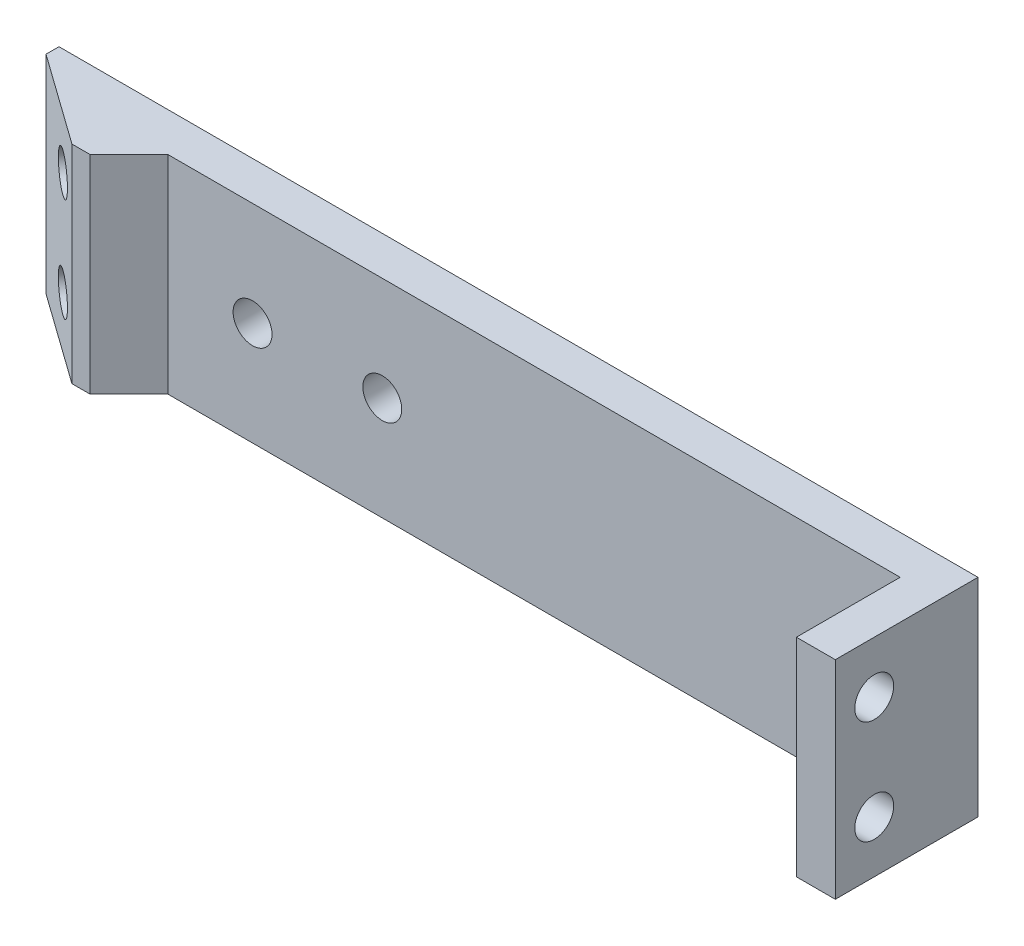
SolidWorks part; units mm, degrees
ref_plane "Front Plane" through (0, 0, 0) normal (0, 0, 1) x (1, 0, 0)
ref_plane "Top Plane" through (0, 0, 0) normal (0, 1, 0) x (1, 0, 0)
ref_plane "Right Plane" through (0, 0, 0) normal (1, 0, 0) x (0, 0, -1)
sketch "Sketch1" plane through (0, 0, 0) normal (0, 0, 1) x (1, 0, 0)
  line L1 (-35.425, -8) -> (35.425, -8)
  line L2 (-35.425, -8) -> (-35.425, 8)
  line L3 (-35.425, 8) -> (35.425, 8)
  line L4 (35.425, -8) -> (35.425, 8)
  line L5 (-35.425, -8) -> (35.425, 8) construction
  line L6 (-35.425, 8) -> (35.425, -8) construction
  point P0 (0, 0)
  dimension "D1" = 70.85
  dimension "D2" = 16
extrude "Boss-Extrude1" add sketch "Sketch1" along normal blind 3
sketch "Sketch2" plane through (0, 0, 3) normal (0, 0, 1) x (1, 0, 0)
  line L0 (-35.425, -8) -> (35.425, -8) construction
  line L1 (-35.425, 8) -> (-27.025, 8)
  line L2 (-35.425, 8) -> (-35.425, -8)
  line L3 (-35.425, -8) -> (-27.025, -8)
  line L4 (-27.025, 8) -> (-27.025, -8)
  dimension "D1" = 8.4
extrude "Boss-Extrude2" add sketch "Sketch2" along normal blind 3
chamfer "Chamfer1" distance 5 distance2 7 1 edges at (-35.425, 0, 6) first distance on face at (-35.425, 0, 3)
sketch "Sketch3" plane through (-12.4409, 0, 17.4172) normal (-0.5812, 0, 0.8137) x (0.8137, 0, 0.5812)
  line L0 (-28.2453, 8) -> (-19.6429, 8) construction
  line L1 (-19.6429, -8) -> (-28.2453, -8) construction
  line L2 (-19.6429, 8) -> (-19.6429, -8) construction
  circle A0 centre (-22.6429, 4) radius 1.5
  circle A1 centre (-22.6429, -4) radius 1.5
  dimension "D1" = 3
  dimension "D2" = 3
  dimension "D3" = 4
  dimension "D4" = 4
  dimension "D6" = 3
  dimension "D5" = 3
extrude "Cut-Extrude1" cut sketch "Sketch3" against normal blind 3
chamfer "Chamfer2" distance 3 angle 45 1 edges at (-27.025, 0, 3)
sketch "Sketch4" plane through (-12.4409, 0, 17.4172) normal (-0.5812, 0, 0.8137) x (0.8137, 0, 0.5812)
  line L1 (-19.4675, 4) -> (-21.0552, 6.75)
  line L2 (-21.0552, 6.75) -> (-24.2307, 6.75)
  line L3 (-24.2307, 6.75) -> (-25.8184, 4)
  line L4 (-25.8184, 4) -> (-24.2307, 1.25)
  line L5 (-24.2307, 1.25) -> (-21.0552, 1.25)
  line L6 (-21.0552, 1.25) -> (-19.4675, 4)
  line L7 (-19.4675, -4) -> (-21.0552, -1.25)
  line L8 (-21.0552, -1.25) -> (-24.2307, -1.25)
  line L9 (-24.2307, -1.25) -> (-25.8184, -4)
  line L10 (-25.8184, -4) -> (-24.2307, -6.75)
  line L11 (-24.2307, -6.75) -> (-21.0552, -6.75)
  line L12 (-21.0552, -6.75) -> (-19.4675, -4)
  circle A0 centre (-22.6429, 4) radius 2.75 construction
  circle A1 centre (-22.6429, -4) radius 2.75 construction
  dimension "D1" = 5.5
  dimension "D2" = 5.5
extrude "Cut-Extrude2" cut sketch "Sketch4" against normal blind 8 from offset 3 offset against normal yes
sketch "Sketch5" plane through (0, 0, 3) normal (0, 0, 1) x (1, 0, 0)
  line L0 (-24.025, -8) -> (35.425, -8) construction
  line L1 (35.425, 8) -> (32.425, 8)
  line L2 (35.425, 8) -> (35.425, -8)
  line L3 (35.425, -8) -> (32.425, -8)
  line L4 (32.425, 8) -> (32.425, -8)
  dimension "D1" = 3
extrude "Boss-Extrude3" add sketch "Sketch5" along normal blind 8
sketch "Sketch6" plane through (35.425, 0, 0) normal (1, 0, 0) x (0, 0, -1)
  line L0 (-11, -8) -> (-11, 8) construction
  line L1 (-11, 8) -> (0, 8) construction
  line L2 (-11, -8) -> (0, -8) construction
  circle A0 centre (-8, 4) radius 1.5
  circle A1 centre (-8, -4) radius 1.5
  dimension "D1" = 3
  dimension "D2" = 3
  dimension "D3" = 3
  dimension "D4" = 3
  dimension "D5" = 4
  dimension "D6" = 4
extrude "Cut-Extrude3" cut sketch "Sketch6" against normal blind 8
sketch "Sketch7" plane through (0, 0, 0) normal (0, 0, -1) x (-1, 0, 0)
  circle A0 centre (17.5, 0) radius 1.5
  dimension "D1" = 3
  dimension "D2" = 17.5
extrude "Cut-Extrude4" cut sketch "Sketch7" against normal blind 10
sketch "Sketch8" plane through (0, 0, 3) normal (0, 0, 1) x (1, 0, 0)
  circle A0 centre (-7.5, 0) radius 1.5
  circle A1 centre (-17.5, 0) radius 1.5 construction
  dimension "D1" = 3
  dimension "D2" = 10
extrude "Cut-Extrude5" cut sketch "Sketch8" against normal blind 10
